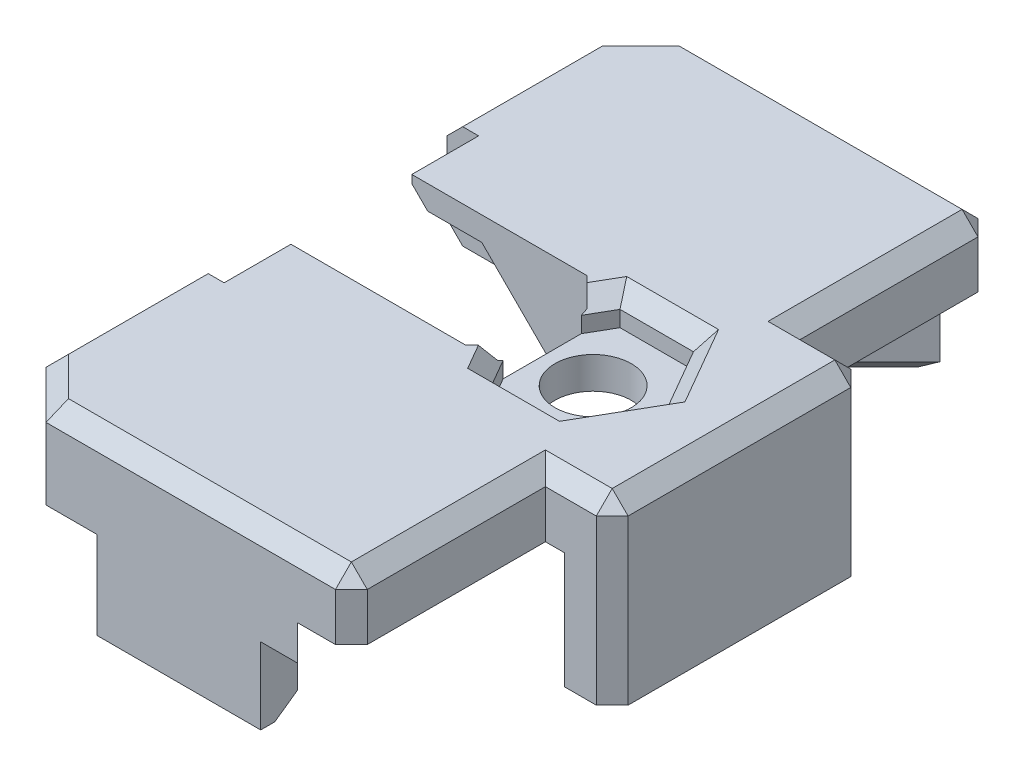
SolidWorks part; units mm, degrees
ref_plane "Front Plane" through (0, 0, 0) normal (0, 0, 1) x (1, 0, 0)
ref_plane "Top Plane" through (0, 0, 0) normal (0, 1, 0) x (1, 0, 0)
ref_plane "Right Plane" through (0, 0, 0) normal (1, 0, 0) x (0, 0, -1)
sketch "Sketch1" plane through (0, 0, 0) normal (0, 1, 0) x (1, 0, 0)
  line L0 (0.6421, 0) -> (50000.6421, 0) construction
  line L4 (-8.6, 4) -> (-8.6, -4)
  line L7 (-8.6, 4) -> (4.6, 4)
  line L8 (4.6, 4) -> (4.6, -4)
  line L9 (4.6, -4) -> (-8.6, -4)
  arc A0 (0, 1.2) -> (0, -1.2) centre (0, 0) ccw
  arc A1 (1.2, 0) -> (0, 1.2) centre (0, 0) ccw
  arc A2 (0, -1.2) -> (1.2, 0) centre (0, 0) ccw
  point P11 (-8.6, 0)
  dimension "D1" = 2.4
  dimension "D2" = 4.6
  dimension "D3" = 8.6
  dimension "D4" = 8
extrude "Boss-Extrude1" add sketch "Sketch1" against normal blind 2
sketch "Sketch2" plane through (0, 0, -4) normal (0, 0, -1) x (-1, 0, 0)
  line L0 (8.6, -2) -> (8.6, -0.75)
  line L1 (8.6, -2) -> (8.6, 0) construction
  line L2 (8.6, -0.75) -> (3.75, -0.75)
  line L3 (3.75, -0.75) -> (2.5, -2)
  line L4 (-4.6, -2) -> (8.6, -2) construction
  line L5 (2.5, -2) -> (8.6, -2)
  line L6 (2.5, -2) -> (2.5, 0) construction
  line L7 (-4.6, 0) -> (8.6, 0) construction
  dimension "D1" = 1.25
  dimension "D2" = 2.5
  dimension "D3" = 45
extrude "Cut-Extrude1" cut sketch "Sketch2" against normal through all both and the other way through all
sketch "Sketch3" plane through (0, -2, 0) normal (0, -1, 0) x (1, 0, 0)
  line L0 (-2.5, 4) -> (4.6, 4) construction
  line L1 (4.6, -4) -> (2.6, -4)
  line L2 (4.6, -4) -> (4.6, 4)
  line L3 (4.6, 4) -> (2.6, 4)
  line L4 (2.6, -4) -> (2.6, 4)
  dimension "D1" = 2
extrude "Boss-Extrude2" add sketch "Sketch3" along normal blind 3.65
sketch "Sketch4" plane through (0, -2, 2) normal (0, 1, 0) x (1, 0, 0)
  line L0 (-2.5, -2) -> (2.6, -2) construction
  line L1 (-8.6, -8.1) -> (0.8, -8.1)
  line L2 (-8.6, -8.1) -> (-8.6, -2)
  line L3 (-8.6, -2) -> (0.8, -2)
  line L4 (0.8, -8.1) -> (0.8, -2) construction
  line L5 (-8.6, -2) -> (-8.6, 6) construction
  line L7 (0.8, -2) -> (2.5, -2)
  line L8 (0.8, -2) -> (0.8, -8.1) construction
  line L9 (0.8, -8.1) -> (2.5, -8.1)
  line L10 (2.5, -2) -> (2.5, -8.1)
  dimension "D1" = 6.1
  dimension "D2" = 9.4
  dimension "D3" = 1.7
extrude "Boss-Extrude3" add sketch "Sketch4" along normal blind 2
sketch "Sketch5" plane through (0, -2, 0) normal (0, -1, 0) x (1, 0, 0)
  line L0 (-8.6, 10.1) -> (-8.6, 4) construction
  line L1 (-8.6, 10.1) -> (-6.6, 10.1)
  line L2 (-8.6, 10.1) -> (-8.6, 4)
  line L3 (-8.6, 4) -> (-6.6, 4)
  line L4 (-6.6, 8.1) -> (-6.6, 4)
  line L6 (-1.2, 8.1) -> (0.8, 10.1)
  line L7 (-6.6, 10.1) -> (-1.2, 10.1)
  line L8 (-6.6, 10.1) -> (-6.6, 8.1) construction
  line L9 (-6.6, 8.1) -> (-1.2, 8.1)
  line L10 (-1.2, 10.1) -> (-1.2, 8.1) construction
  line L11 (-8.6, 4) -> (-2.5, 4) construction
  line L12 (0.8, 10.1) -> (-1.2, 10.1)
  line L13 (-6.6, 10.1) -> (-6.6, 8.1) construction
  line L15 (-8.6, 10.1) -> (2.5, 10.1) construction
  dimension "D1" = 2
  dimension "D2" = 2
  dimension "D3" = 45
  dimension "D4" = 5.4
extrude "Boss-Extrude4" add sketch "Sketch5" along normal blind 1.25
sketch "Sketch6" plane through (0, 0, 4) normal (0, 0, -1) x (-1, 0, 0)
  line L0 (2.5, -2) -> (2.5, -3.65)
  line L1 (2.5, -3.65) -> (5.4, -0.75)
  line L2 (8.6, -0.75) -> (3.75, -0.75) construction
  line L3 (2.5, -2) -> (3.75, -0.75)
  line L4 (3.75, -0.75) -> (5.4, -0.75)
  dimension "D1" = 2.9
  dimension "D2" = 2.9
extrude "Boss-Extrude5" add sketch "Sketch6" along normal blind 2.1
sketch "Sketch8" plane through (0, -3.25, 0) normal (0, -1, 0) x (1, 0, 0)
  line L0 (0.8, 10.1) -> (-1.2, 8.1)
  line L1 (-1.2, 8.1) -> (-6, 8.1)
  line L2 (-6.6, 8.1) -> (-1.2, 8.1) construction
  line L3 (-6, 8.1) -> (-6, 10.1)
  line L4 (0.8, 10.1) -> (-8.6, 10.1) construction
  line L5 (-6, 10.1) -> (0.8, 10.1)
  line L6 (-8.6, 10.1) -> (-8.6, 4) construction
  dimension "D1" = 2.6
extrude "Boss-Extrude6" add sketch "Sketch8" along normal blind 2.25
chamfer "Chamfer3" distance 1.5 angle 45 1 edges at (-8.6, -1.625, 10.1)
chamfer "Chamfer4" distance 0.3 angle 45 1 edges at (-6.6, -2.625, 8.1)
mirror "Mirror1" about plane through (0, 0, 0) normal (0, 0, 1) of "Boss-Extrude6", "Boss-Extrude3", "Boss-Extrude4", "Boss-Extrude5", "Chamfer4", "Chamfer3"
sketch "Sketch10" plane through (0, -0.75, 0) normal (0, -1, 0) x (1, 0, 0)
  line L0 (-8.6, -4) -> (-5.4, -4) construction
  line L1 (-8.6, 4) -> (-7.6, 4)
  line L2 (-8.6, 4) -> (-8.6, -4)
  line L3 (-8.6, -4) -> (-7.6, -4)
  line L4 (-7.6, 4) -> (-7.6, -4)
  dimension "D1" = 1
extrude "Cut-Extrude2" cut sketch "Sketch10" against normal through all both and the other way through all contours L2 L1 L4 L3
sketch "Sketch11" plane through (0, 0, 0) normal (0, 1, 0) x (1, 0, 0)
  line L2 (0, -1.9) -> (0, 1.9) construction
  line L4 (1.1547, -2) -> (-1.1547, -2)
  line L5 (1.1547, 2) -> (-1.1547, 2)
  line L6 (1.1547, -2) -> (2.3094, 0)
  line L7 (2.3094, 0) -> (1.1547, 2)
  line L8 (-1.1547, -2) -> (-1.2124, -1.9)
  line L9 (-1.2124, 1.9) -> (-1.1547, 2)
  line L10 (0, 1.9) -> (-1.2124, 1.9) construction
  line L11 (-2.3094, 0) -> (-1.2124, 1.9)
  line L12 (-1.2124, -1.9) -> (-2.3094, 0)
  line L13 (-1.2124, -1.9) -> (0, -1.9) construction
  arc A0 (-1.1547, 2) -> (-1.3128, 1.9) centre (0, 0) ccw construction
  arc A1 (-1.1547, -2) -> (1.1547, -2) centre (0, 0) ccw construction
  arc A2 (1.1547, -2) -> (2.3094, 0) centre (0, 0) ccw construction
  arc A3 (2.3094, 0) -> (1.1547, 2) centre (0, 0) ccw construction
  arc A4 (1.1547, 2) -> (-1.1547, 2) centre (0, 0) ccw construction
  arc A5 (-1.3128, 1.9) -> (-2.3094, 0) centre (0, 0) ccw construction
  arc A6 (-1.3128, -1.9) -> (-1.1547, -2) centre (0, 0) ccw construction
  arc A7 (-2.3094, 0) -> (-1.3128, -1.9) centre (0, 0) ccw construction
  dimension "D3" = 4
extrude "Cut-Extrude3" cut sketch "Sketch11" against normal blind 1 and the other way through all
sketch "Sketch12" plane through (0, 0, 0) normal (0, 1, 0) x (1, 0, 0)
  line L0 (-7.6, -1.9) -> (-1.6, -1.9)
  line L1 (-7.6, -4) -> (-7.6, 4) construction
  line L3 (-1.6, -1.9) -> (-1.6, 1.9)
  line L5 (-1.6, 1.9) -> (-7.6, 1.9)
  line L6 (-7.6, 1.9) -> (-7.6, -1.9)
  dimension "D1" = 1.9
  dimension "D2" = 6
extrude "Cut-Extrude4" cut sketch "Sketch12" against normal through all
sketch "Sketch13" plane through (0, 0, 10.1) normal (0, 0, 1) x (1, 0, 0)
  line L1 (0.8, -5.5) -> (-0.35, -5.5)
  line L2 (0.8, -5.5) -> (0.8, -3.1)
  line L3 (0.8, -3.1) -> (-0.35, -3.1)
  line L4 (-0.35, -5.5) -> (-0.35, -3.1)
  dimension "D1" = 2.4
  dimension "D2" = 1.15
extrude "Cut-Extrude5" cut sketch "Sketch13" against normal up to next
chamfer "Chamfer7" distance 0.5 angle 45 50 edges at (-6.6, -3.25, -5.9) (-6.45, -3.25, -7.95) (-6.15, -3.25, -8.1) (-6.15, -3.25, 8.1) (-6.45, -3.25, 7.95) (-6.6, -3.25, 5.9) (-8.6, -3.25, 6.3) (-7.85, -3.25, 9.35) (-6.55, -3.25, 10.1) (-6, -4.375, 10.1) (-6, -4.375, -10.1) (-6.55, -3.25, -10.1) (-7.85, -3.25, -9.35) (-8.6, -3.25, -6.3) (-3.6, -5.5, 8.1) (-0.775, -5.5, 8.525) (-0.2, -5.5, -9.1) (-3.6, -5.5, -8.1) (2.6, -3.825, 4) (2.6, -3.825, -4) (2.6, -5.65, 0) (-2.5, -3.65, -2.95) (-2.5, -3.65, 2.95) (-1.3774, 0, 1.6144) (0, 0, 2) (1.7321, 0, 1) (1.7321, 0, -1) (0, 0, -2) (-1.3774, 0, -1.6144) (4.6, -2.825, -4) (4.6, -2.825, 4) (-8.6, 0, -6.3) (-7.85, 0, -9.35) (-8.6, 0, 6.3) (-7.85, 0, 9.35) (-2.3, 0, -10.1) (2.5, 0, -7.05) (3.55, 0, -4) (4.6, 0, 0) (3.55, 0, 4) (2.5, 0, 7.05) (-2.3, 0, 10.1) (2.5, -1, -10.1) (2.5, -1, 10.1) (-6, -4.375, 8.1) (-6, -4.375, -8.1) (-7.6, -0.75, 2.95) (-7.6, -0.75, -2.95) (-1.6, -1, 1.9) (-1.6, -1, -1.9)
sketch "Sketch14" plane through (0, -3.25, 0) normal (0, -1, 0) x (1, 0, 0)
  line L0 (-8.6, -6.725) -> (-6.6, -6.725)
  line L1 (-8.6, -8.6) -> (-8.6, -4) construction
  line L2 (-6.6, -4) -> (-6.6, -7.8) construction
  line L3 (-6.6, -6.725) -> (-6.6, -5.475)
  line L4 (-6.6, -5.475) -> (-8.6, -5.475)
  line L5 (-8.6, -5.475) -> (-8.6, -6.725)
  line L6 (-8.6, -6.1) -> (-6.6, -6.1) construction
  line L7 (-5.5, -8.1) -> (-1.2, -8.1) construction
  line L8 (0, 0) -> (-1.6, 0) construction
  line L9 (-1.6, -1.4) -> (-1.6, 1.4) construction
  line L10 (-6.6, 5.475) -> (-8.6, 5.475)
  line L11 (-6.6, 6.725) -> (-6.6, 5.475)
  line L12 (-8.6, 6.725) -> (-6.6, 6.725)
  line L13 (-8.6, 5.475) -> (-8.6, 6.725)
  line L14 (-8.6, 6.1) -> (-6.6, 6.1) construction
  dimension "D1" = 2
  dimension "D2" = 1.25
extrude "Cut-Extrude6" cut sketch "Sketch14" against normal up to surface (1.25 mm away) up to face at (-1.3367, -2, 0)
chamfer "Chamfer8" distance 0.5 angle 45 2 edges at (-8.6, -2, 6.1) (-8.6, -2, -6.1)
